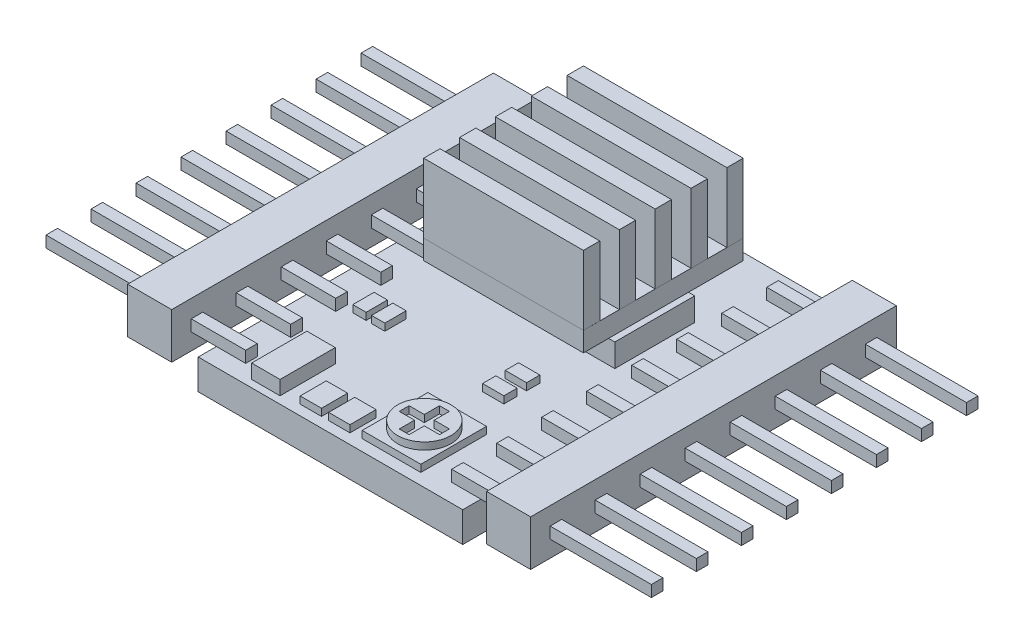
SolidWorks part; units mm, degrees
ref_plane "Front Plane" through (0, 0, 0) normal (0, 0, 1) x (1, 0, 0)
ref_plane "Top Plane" through (0, 0, 0) normal (0, 1, 0) x (1, 0, 0)
ref_plane "Right Plane" through (0, 0, 0) normal (1, 0, 0) x (0, 0, -1)
sketch "Sketch1" plane through (0, 0, 0) normal (0, 1, 0) x (1, 0, 0)
  line L1 (0, 0) -> (14.9, 0)
  line L2 (0, 0) -> (0, 20.45)
  line L3 (0, 20.45) -> (14.9, 20.45)
  line L4 (14.9, 0) -> (14.9, 20.45)
  dimension "D1" = 14.9
  dimension "D2" = 20.45
extrude "Board" add sketch "Sketch1" along normal blind 1.7
sketch "Sketch2" plane through (0, 1.7, 0) normal (0, 1, 0) x (1, 0, 0)
  line L0 (7.45, 20.45) -> (7.45, 0) construction
  line L1 (14.9, 20.45) -> (0, 20.45) construction
  line L2 (0, 0) -> (14.9, 0) construction
  line L3 (24.5, 18.775) -> (24.5, 16.8893) construction
  line L4 (13.25, 18.775) -> (24.5, 18.775)
  line L5 (13.25, 18.775) -> (13.25, 19.425)
  line L6 (13.25, 19.425) -> (24.5, 19.425)
  line L7 (24.5, 18.775) -> (24.5, 19.425)
  line L8 (13.25, 16.8893) -> (24.5, 16.8893)
  line L9 (13.25, 16.8893) -> (13.25, 16.2393)
  line L10 (13.25, 16.2393) -> (24.5, 16.2393)
  line L11 (24.5, 16.8893) -> (24.5, 16.2393)
  line L12 (13.25, 14.3536) -> (24.5, 14.3536)
  line L13 (13.25, 14.3536) -> (13.25, 13.7036)
  line L14 (13.25, 13.7036) -> (24.5, 13.7036)
  line L15 (24.5, 14.3536) -> (24.5, 13.7036)
  line L16 (13.25, 11.8179) -> (24.5, 11.8179)
  line L17 (13.25, 11.8179) -> (13.25, 11.1679)
  line L18 (13.25, 11.1679) -> (24.5, 11.1679)
  line L19 (24.5, 11.8179) -> (24.5, 11.1679)
  line L20 (13.25, 9.2821) -> (24.5, 9.2821)
  line L21 (13.25, 9.2821) -> (13.25, 8.6321)
  line L22 (13.25, 8.6321) -> (24.5, 8.6321)
  line L23 (24.5, 9.2821) -> (24.5, 8.6321)
  line L24 (13.25, 6.7464) -> (24.5, 6.7464)
  line L25 (13.25, 6.7464) -> (13.25, 6.0964)
  line L26 (13.25, 6.0964) -> (24.5, 6.0964)
  line L27 (24.5, 6.7464) -> (24.5, 6.0964)
  line L28 (13.25, 4.2107) -> (24.5, 4.2107)
  line L29 (13.25, 4.2107) -> (13.25, 3.5607)
  line L30 (13.25, 3.5607) -> (24.5, 3.5607)
  line L31 (24.5, 4.2107) -> (24.5, 3.5607)
  line L32 (13.25, 1.675) -> (24.5, 1.675)
  line L33 (13.25, 1.675) -> (13.25, 1.025)
  line L34 (13.25, 1.025) -> (24.5, 1.025)
  line L35 (24.5, 1.675) -> (24.5, 1.025)
  line L36 (24.5, 16.2393) -> (24.5, 14.3536) construction
  line L37 (24.5, 13.7036) -> (24.5, 11.8179) construction
  line L38 (24.5, 11.1679) -> (24.5, 9.2821) construction
  line L39 (24.5, 8.6321) -> (24.5, 6.7464) construction
  line L40 (24.5, 6.0964) -> (24.5, 4.2107) construction
  line L41 (24.5, 3.5607) -> (24.5, 1.675) construction
  line L42 (13.25, 1.025) -> (13.25, 0) construction
  line L43 (13.25, 20.45) -> (13.25, 19.425) construction
  line L44 (13.25, 1.675) -> (13.25, 3.5607) construction
  line L45 (13.25, 4.2107) -> (13.25, 6.0964) construction
  line L46 (13.25, 6.7464) -> (13.25, 8.6321) construction
  line L47 (13.25, 9.2821) -> (13.25, 11.1679) construction
  line L48 (13.25, 11.8179) -> (13.25, 13.7036) construction
  line L49 (13.25, 14.3536) -> (13.25, 16.2393) construction
  line L50 (13.25, 16.8893) -> (13.25, 18.775) construction
  line L52 (1.65, 16.8893) -> (1.65, 18.775) construction
  line L53 (1.65, 14.3536) -> (1.65, 16.2393) construction
  line L54 (1.65, 11.8179) -> (1.65, 13.7036) construction
  line L55 (1.65, 9.2821) -> (1.65, 11.1679) construction
  line L56 (1.65, 6.7464) -> (1.65, 8.6321) construction
  line L57 (1.65, 4.2107) -> (1.65, 6.0964) construction
  line L58 (1.65, 1.675) -> (1.65, 3.5607) construction
  line L59 (1.65, 20.45) -> (1.65, 19.425) construction
  line L60 (1.65, 1.025) -> (1.65, 0) construction
  line L61 (-9.6, 3.5607) -> (-9.6, 1.675) construction
  line L62 (-9.6, 6.0964) -> (-9.6, 4.2107) construction
  line L63 (-9.6, 8.6321) -> (-9.6, 6.7464) construction
  line L64 (-9.6, 11.1679) -> (-9.6, 9.2821) construction
  line L65 (-9.6, 13.7036) -> (-9.6, 11.8179) construction
  line L66 (-9.6, 16.2393) -> (-9.6, 14.3536) construction
  line L67 (-9.6, 18.775) -> (-9.6, 16.8893) construction
  line L68 (-9.6, 1.675) -> (-9.6, 1.025)
  line L69 (1.65, 1.025) -> (-9.6, 1.025)
  line L70 (1.65, 1.675) -> (1.65, 1.025)
  line L71 (1.65, 1.675) -> (-9.6, 1.675)
  line L72 (-9.6, 4.2107) -> (-9.6, 3.5607)
  line L73 (1.65, 3.5607) -> (-9.6, 3.5607)
  line L74 (1.65, 4.2107) -> (1.65, 3.5607)
  line L75 (1.65, 4.2107) -> (-9.6, 4.2107)
  line L76 (-9.6, 6.7464) -> (-9.6, 6.0964)
  line L77 (1.65, 6.0964) -> (-9.6, 6.0964)
  line L78 (1.65, 6.7464) -> (1.65, 6.0964)
  line L79 (1.65, 6.7464) -> (-9.6, 6.7464)
  line L80 (-9.6, 9.2821) -> (-9.6, 8.6321)
  line L81 (1.65, 8.6321) -> (-9.6, 8.6321)
  line L82 (1.65, 9.2821) -> (1.65, 8.6321)
  line L83 (1.65, 9.2821) -> (-9.6, 9.2821)
  line L84 (-9.6, 11.8179) -> (-9.6, 11.1679)
  line L85 (1.65, 11.1679) -> (-9.6, 11.1679)
  line L86 (1.65, 11.8179) -> (1.65, 11.1679)
  line L87 (1.65, 11.8179) -> (-9.6, 11.8179)
  line L88 (-9.6, 14.3536) -> (-9.6, 13.7036)
  line L89 (1.65, 13.7036) -> (-9.6, 13.7036)
  line L90 (1.65, 14.3536) -> (1.65, 13.7036)
  line L91 (1.65, 14.3536) -> (-9.6, 14.3536)
  line L92 (-9.6, 16.8893) -> (-9.6, 16.2393)
  line L93 (1.65, 16.2393) -> (-9.6, 16.2393)
  line L94 (1.65, 16.8893) -> (1.65, 16.2393)
  line L95 (1.65, 16.8893) -> (-9.6, 16.8893)
  line L96 (-9.6, 18.775) -> (-9.6, 19.425)
  line L97 (1.65, 19.425) -> (-9.6, 19.425)
  line L98 (1.65, 18.775) -> (1.65, 19.425)
  line L99 (1.65, 18.775) -> (-9.6, 18.775)
  point P9 (0, 0)
  point P11 (13.3574, 0.6)
  dimension "D1" = 0.65
  dimension "D2" = 18.4
  dimension "D3" = 9.6
  dimension "D4" = 11.25
extrude "HeaderPins" add sketch "Sketch2" along normal blind 0.64
sketch "Sketch3" plane through (0, 1.7, 0) normal (0, 1, 0) x (1, 0, 0)
  line L0 (7.45, 20.45) -> (7.45, 18.75) construction
  line L1 (14.9, 20.45) -> (0, 20.45) construction
  line L3 (2.95, 9.75) -> (11.95, 9.75)
  line L4 (2.95, 9.75) -> (2.95, 18.75)
  line L5 (2.95, 18.75) -> (11.95, 18.75)
  line L6 (11.95, 9.75) -> (11.95, 18.75)
  point P8 (7.45, 18.75)
  dimension "D1" = 1.7
  dimension "D2" = 9
extrude "HeatSink" add sketch "Sketch3" along normal blind 1.1 from offset 1.3
sketch "Sketch4" plane through (0, 4.1, 0) normal (0, 1, 0) x (1, 0, 0)
  line L1 (2.95, 9.75) -> (11.9487, 9.75)
  line L2 (2.95, 9.75) -> (2.95, 10.67)
  line L3 (2.95, 10.67) -> (11.9487, 10.67)
  line L4 (11.9487, 9.75) -> (11.9487, 10.67)
  line L5 (2.95, 18.75) -> (2.95, 9.75) construction
  line L6 (2.95, 18.75) -> (11.95, 18.75)
  line L7 (2.95, 18.75) -> (2.95, 17.83)
  line L8 (2.95, 17.83) -> (11.95, 17.83)
  line L9 (11.95, 18.75) -> (11.95, 17.83)
  line L10 (2.95, 16.73) -> (11.95, 16.73)
  line L11 (2.95, 16.73) -> (2.95, 15.81)
  line L12 (2.95, 15.81) -> (11.95, 15.81)
  line L13 (11.95, 16.73) -> (11.95, 15.81)
  line L15 (2.95, 14.71) -> (11.95, 14.71)
  line L16 (2.95, 14.71) -> (2.95, 13.79)
  line L17 (2.95, 13.79) -> (11.95, 13.79)
  line L18 (11.95, 14.71) -> (11.95, 13.79)
  line L19 (8.3615, 10.67) -> (8.3615, 11.77) construction
  line L20 (11.95, 12.69) -> (2.95, 12.69)
  line L21 (11.95, 12.69) -> (11.95, 11.77)
  line L22 (11.95, 11.77) -> (2.95, 11.77)
  line L23 (2.95, 12.69) -> (2.95, 11.77)
  line L24 (8.3615, 12.69) -> (8.3615, 13.79) construction
  line L25 (8.3615, 14.71) -> (8.3615, 15.81) construction
  line L26 (8.3615, 16.73) -> (8.3615, 17.83) construction
  line L27 (11.95, 9.75) -> (11.95, 18.75) construction
  line L28 (2.95, 9.75) -> (11.95, 9.75) construction
  point P5 (3.2089, 9.8764)
  point P6 (2.95, 8.9)
  point P22 (2.95, 17.9)
  point P23 (11.95, 17.9)
  point P28 (0, 0)
  point P41 (11.9299, 8.9)
  point P44 (11.9487, 8.9)
  point P45 (11.95, 10.92)
  point P46 (11.95, 12.94)
  point P47 (11.95, 14.96)
  dimension "D1" = 0.92
extrude "HeatSinkFins" add sketch "Sketch4" along normal blind 3.9
sketch "Sketch5" plane through (0, 1.7, 0) normal (0, 1, 0) x (1, 0, 0)
  line L0 (0, 8.6321) -> (0, 6.7464) construction
  line L1 (2.1966, 6.5109) -> (2.9466, 6.5109)
  line L2 (2.1966, 6.5109) -> (2.1966, 7.7109)
  line L3 (2.1966, 7.7109) -> (2.9466, 7.7109)
  line L4 (2.9466, 6.5109) -> (2.9466, 7.7109)
  line L5 (3.25, 6.5109) -> (4, 6.5109)
  line L6 (3.25, 6.5109) -> (3.25, 7.7109)
  line L7 (3.25, 7.7109) -> (4, 7.7109)
  line L8 (4, 6.5109) -> (4, 7.7109)
  line L9 (9.7, 7.5943) -> (10.9, 7.5943)
  line L10 (9.7, 7.5943) -> (9.7, 8.3443)
  line L11 (9.7, 8.3443) -> (10.9, 8.3443)
  line L12 (10.9, 7.5943) -> (10.9, 8.3443)
  line L13 (10.9, 7.0656) -> (9.7, 7.0656)
  line L14 (10.9, 7.0656) -> (10.9, 6.3156)
  line L15 (10.9, 6.3156) -> (9.7, 6.3156)
  line L16 (9.7, 7.0656) -> (9.7, 6.3156)
  line L17 (14.9, 4.2107) -> (14.9, 6.0964) construction
  line L18 (14.9, 1.675) -> (14.9, 3.5607) construction
  line L19 (2.5984, 0.4104) -> (4.1984, 0.4104)
  line L20 (2.5984, 0.4104) -> (2.5984, 3.5204)
  line L21 (2.5984, 3.5204) -> (4.1984, 3.5204)
  line L22 (4.1984, 0.4104) -> (4.1984, 3.5204)
  line L23 (5.1709, 0.5717) -> (6.3709, 0.5717)
  line L24 (5.1709, 0.5717) -> (5.1709, 2.0439)
  line L25 (5.1709, 2.0439) -> (6.3709, 2.0439)
  line L26 (6.3709, 0.5717) -> (6.3709, 2.0439)
  line L27 (6.7745, 0.5717) -> (7.9745, 0.5717)
  line L28 (6.7745, 0.5717) -> (6.7745, 2.0439)
  line L29 (6.7745, 2.0439) -> (7.9745, 2.0439)
  line L30 (7.9745, 0.5717) -> (7.9745, 2.0439)
  line L31 (8.6, 4.3363) -> (11.9, 4.3363)
  line L32 (8.6, 4.3363) -> (8.6, 0.6363)
  line L33 (8.6, 0.6363) -> (11.9, 0.6363)
  line L34 (11.9, 4.3363) -> (11.9, 0.6363)
  point P36 (11.8567, 3.6775)
  point P37 (7.9241, 2.0036)
  point P38 (6.835, 2.0238)
  point P39 (5.9073, 2.0238)
  point P40 (4.8183, 2.0439)
  point P41 (6.7745, 2.0439)
  point P42 (6.109, 2.0439)
  point P43 (4.9191, 2.0843)
  point P44 (4.0116, 2.3263)
  point P45 (2.3377, 2.4675)
  point P46 (4.0318, 0.4104)
  point P47 (12.3439, 4.3363)
  point P50 (9.7, 7.5943)
  point P51 (6.3709, 2.0439)
  point P52 (4.1703, 2.4501)
  point P53 (2.5984, 2.5359)
  dimension "D1" = 1.2
  dimension "D2" = 0.75
  dimension "D3" = 4
  dimension "D4" = 5.2
  dimension "D5" = 3.3
  dimension "D6" = 3.7
  dimension "D7" = 6.3
  dimension "D8" = 1.2
  dimension "D9" = 1.6
  dimension "D10" = 3.11
extrude "Components" add sketch "Sketch5" along normal blind 0.4
sketch "Sketch6" plane through (0, 2.1, 0) normal (0, 1, 0) x (1, 0, 0)
  line L0 (8.6, 0.6363) -> (11.9, 4.3363) construction
  line L1 (2.5984, 0.4104) -> (4.1984, 0.4104)
  line L2 (2.5984, 0.4104) -> (2.5984, 3.5204)
  line L3 (2.5984, 3.5204) -> (4.1984, 3.5204)
  line L4 (4.1984, 0.4104) -> (4.1984, 3.5204)
  line L5 (9.1147, 2.7644) -> (9.972, 2.5544) construction
  line L6 (9.972, 1.351) -> (10.528, 1.351)
  line L7 (9.972, 1.351) -> (9.972, 2.2083)
  line L8 (9.972, 3.6217) -> (10.528, 3.6217)
  line L9 (10.528, 1.351) -> (10.528, 2.2083)
  line L10 (9.972, 1.351) -> (10.528, 3.6217) construction
  line L11 (9.972, 3.6217) -> (10.528, 1.351) construction
  line L12 (9.1147, 2.7644) -> (9.972, 2.7644)
  line L13 (9.1147, 2.7644) -> (9.1147, 2.2083)
  line L14 (9.1147, 2.2083) -> (10.002, 2.2083)
  line L15 (11.3853, 2.7644) -> (11.3853, 2.2083)
  line L16 (9.972, 2.5544) -> (11.3853, 2.2083) construction
  line L17 (9.1147, 2.2083) -> (11.3853, 2.7644) construction
  line L18 (9.972, 2.5544) -> (9.972, 2.7644) construction
  line L19 (9.972, 2.7644) -> (9.972, 3.6217)
  line L20 (9.972, 2.7644) -> (10.1819, 2.7644) construction
  line L21 (10.498, 2.7644) -> (11.3853, 2.7644)
  line L22 (10.1819, 2.7644) -> (10.3181, 2.7644) construction
  line L23 (10.3181, 2.7644) -> (10.498, 2.7644) construction
  line L24 (10.528, 2.5544) -> (10.528, 2.7644) construction
  line L25 (10.528, 2.7644) -> (10.528, 3.6217)
  line L26 (10.528, 2.4182) -> (10.528, 2.5544) construction
  line L27 (10.528, 2.2083) -> (10.528, 2.4182) construction
  line L28 (10.3181, 2.2083) -> (10.528, 2.2083) construction
  line L29 (10.528, 2.2083) -> (11.3853, 2.2083)
  line L30 (10.1819, 2.2083) -> (10.3181, 2.2083) construction
  line L31 (10.002, 2.2083) -> (10.1819, 2.2083) construction
  line L32 (9.972, 2.2083) -> (9.972, 2.4182) construction
  line L33 (9.972, 2.4182) -> (9.972, 2.5544) construction
  circle A0 centre (10.25, 2.4863) radius 1.5017
  point P10 (10.25, 2.4863)
  line M8 (2.5984, 3.5204) -> (2.5984, 0.4104)
  line M9 (2.5984, 0.4104) -> (4.1984, 0.4104)
  line M10 (4.1984, 0.4104) -> (4.1984, 3.5204)
  line M11 (4.1984, 3.5204) -> (2.5984, 3.5204)
extrude "Components2" add sketch "Sketch6" along normal blind 0.4 contours M11 M8 M9 M10 | A0 L29 L9 L6 L7 L14 L13 L12 L19 L8 L25 L21 L15 region at (3.3984, 2.1, -1.9654) region at (8.7908, 2.1, -2.4863)
sketch "Sketch7" plane through (0, 3, 0) normal (0, -1, 0) x (1, 0, 0)
  line L0 (11.95, -9.75) -> (11.95, -17.0823) construction
  line L1 (2.6, -15.6662) -> (12.3, -15.6662)
  line L2 (2.6, -15.6662) -> (2.6, -11.1662)
  line L3 (2.6, -11.1662) -> (12.3, -11.1662)
  line L4 (12.3, -15.6662) -> (12.3, -11.1662)
  line L5 (2.95, -9.75) -> (2.95, -18.75) construction
  line L6 (11.95, -13.4162) -> (12.3, -13.4162) construction
  line L7 (2.6, -12.4389) -> (2.95, -12.4389) construction
  point P4 (2.95, -18.75)
  point P5 (2.95, -9.75)
  point P7 (11.95, -9.75)
  point P9 (11.95, -18.75)
  point P16 (11.95, -13.4162)
  dimension "D1" = 9.7
  dimension "D2" = 4.5
extrude "MainIC" add sketch "Sketch7" along normal up to next
sketch "Sketch8" plane through (0, 2.34, 0) normal (0, 1, 0) x (1, 0, 0)
  line L0 (-2.66, -0.075) -> (-2.66, 1.025) construction
  line L1 (-1.42, 20.525) -> (-3.9, 20.525)
  line L2 (-1.42, 20.525) -> (-1.42, -0.075)
  line L3 (-1.42, -0.075) -> (-3.9, -0.075)
  line L4 (-3.9, 20.525) -> (-3.9, -0.075)
  line L5 (-9.6, 1.025) -> (1.65, 1.025) construction
  line L6 (-2.66, 20.525) -> (-2.66, 19.425) construction
  line L7 (1.65, 19.425) -> (-9.6, 19.425) construction
  line L8 (7.45, 20.45) -> (7.45, 0) construction
  line L9 (14.9, 20.45) -> (0, 20.45) construction
  line L10 (0, 0) -> (14.9, 0) construction
  line L11 (-9.6, 6.7464) -> (-9.6, 6.0964) construction
  line L12 (17.56, 20.525) -> (17.56, 19.425) construction
  line L13 (17.56, -0.075) -> (17.56, 1.025) construction
  line L14 (18.8, 20.525) -> (18.8, -0.075)
  line L15 (16.32, -0.075) -> (18.8, -0.075)
  line L16 (16.32, 20.525) -> (16.32, -0.075)
  line L17 (16.32, 20.525) -> (18.8, 20.525)
  dimension "D1" = 5.7
  dimension "D2" = 2.48
  dimension "D3" = 20.6
extrude "HeaderPlastic" add sketch "Sketch8" against normal blind 2.57 from offset 1
